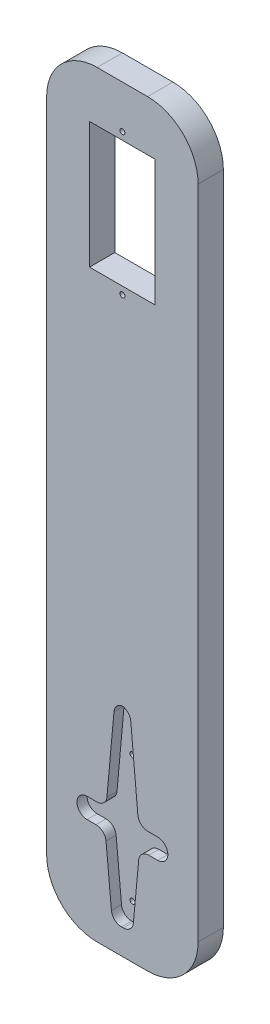
SolidWorks part; units mm, degrees
ref_plane "Přední rovina" through (0, 0, 0) normal (0, 0, 1) x (1, 0, 0)
ref_plane "Horní rovina" through (0, 0, 0) normal (0, 1, 0) x (1, 0, 0)
ref_plane "Pravá rovina" through (0, 0, 0) normal (1, 0, 0) x (0, 0, -1)
sketch "Skica1" plane through (0, 0, 0) normal (0, 0, 1) x (1, 0, 0)
  line L1 (0, 0) -> (30, 0)
  line L2 (0, 0) -> (0, 150)
  line L3 (0, 150) -> (30, 150)
  line L4 (30, 0) -> (30, 150)
  dimension "D1" = 150
  dimension "D2" = 30
extrude "Přidat vysunutím1" add sketch "Skica1" along normal blind 5
fillet "Zaoblit1" radius 10 4 edges at (30, 0, 2.5) (0, 0, 2.5) (30, 150, 2.5) (0, 150, 2.5)
sketch "Skica2" plane through (0, 0, 5) normal (0, 0, 1) x (1, 0, 0)
  line L1 (8.5, 140) -> (21.5, 140)
  line L2 (8.5, 140) -> (8.5, 115)
  line L3 (8.5, 115) -> (21.5, 115)
  line L4 (21.5, 140) -> (21.5, 115)
  line L5 (20, 150) -> (10, 150) construction
  point P4 (15, 150)
  point P7 (15, 140)
  dimension "D1" = 13
  dimension "D2" = 25
  dimension "D3" = 10
extrude "Odebrat vysunutím1" cut sketch "Skica2" against normal through all
sketch "Skica3" plane through (0, 0, 5) normal (0, 0, 1) x (1, 0, 0)
  line L0 (21.5, 140) -> (8.5, 140) construction
  line L2 (8.5, 140) -> (8.5, 115) construction
  line L3 (8.5, 127.5) -> (21.5, 127.5) construction
  line L4 (21.5, 115) -> (21.5, 140) construction
  circle A0 centre (15, 141.5) radius 0.5
  circle A1 centre (15, 113.5) radius 0.5
  point P4 (15, 140)
  point P9 (8.5, 127.5)
  dimension "D1" = 1
  dimension "D2" = 14
  dimension "D3" = 28
extrude "Odebrat vysunutím2" cut sketch "Skica3" against normal through all
sketch "Skica4" plane through (0, 0, 5) normal (0, 0, 1) x (1, 0, 0)
  line L0 (11.5, 21) -> (18.5, 21)
  line L1 (18.5, 21) -> (16.5, 43)
  line L3 (13.5, 43) -> (11.5, 21)
  line L4 (13.5, 43) -> (16.5, 43)
  line L5 (11.5, 21) -> (13, 5)
  line L6 (13, 5) -> (17, 5)
  line L7 (17, 5) -> (18.5, 21)
  line L8 (10, 0) -> (20, 0) construction
  line L10 (8, 24) -> (22, 24)
  line L11 (8, 24) -> (8, 20)
  line L12 (8, 20) -> (22, 20)
  line L13 (22, 24) -> (22, 20)
  arc A0 (8, 24) -> (8, 20) centre (8, 22) ccw
  arc A1 (22, 24) -> (22, 20) centre (22, 22) cw
  point P2 (15, 43)
  point P5 (15, 21)
  point P6 (15, 5)
  point P11 (15, 0)
  point P16 (15, 24)
  dimension "D1" = 7
  dimension "D2" = 3
  dimension "D3" = 22
  dimension "D4" = 16
  dimension "D5" = 5
  dimension "D6" = 4
  dimension "D7" = 19
  dimension "D8" = 14
  dimension "D9" = 4
extrude "Odebrat vysunutím3" cut sketch "Skica4" against normal blind 2 contours L12 L5 L6 L7 | L5 L12 L7 L0 | L11 L12 L5 L3 L10 | L10 L3 L0 L1 | L13 L10 L1 L7 L12 | A1 L13 | L11 A0 | L3 L10 L1 L4 region at (15, 22.4797, 5) region at (9.8079, 22.0229, 5) region at (15, 20.5023, 5) region at (20.1921, 22.0229, 5) region at (15, 32.3429, 5) region at (15, 13.1503, 5) region at (7.1512, 22, 5) region at (22.8488, 22, 5)
sketch "Skica5" plane through (0, 0, 3) normal (0, 0, 1) x (1, 0, 0)
  line L1 (13.5, 43) -> (16.5, 43) construction
  line L2 (13, 5) -> (17, 5) construction
  circle A0 centre (15, 33.6) radius 0.5
  circle A1 centre (15, 8.5) radius 0.5
  point P4 (0, 0)
  point P5 (0, 0)
  point P10 (15, 43)
  dimension "D1" = 1
  dimension "D2" = 1
  dimension "D4" = 3.5
  dimension "D3" = 25.1
extrude "Odebrat vysunutím4" cut sketch "Skica5" against normal through all
fillet "Zaoblit2" radius 2 8 edges at (16.5, 43, 4) (13.5, 43, 4) (18.2273, 24, 4) (18.4062, 20, 4) (17, 5, 4) (13, 5, 4) (11.7727, 24, 4) (11.5937, 20, 4)
